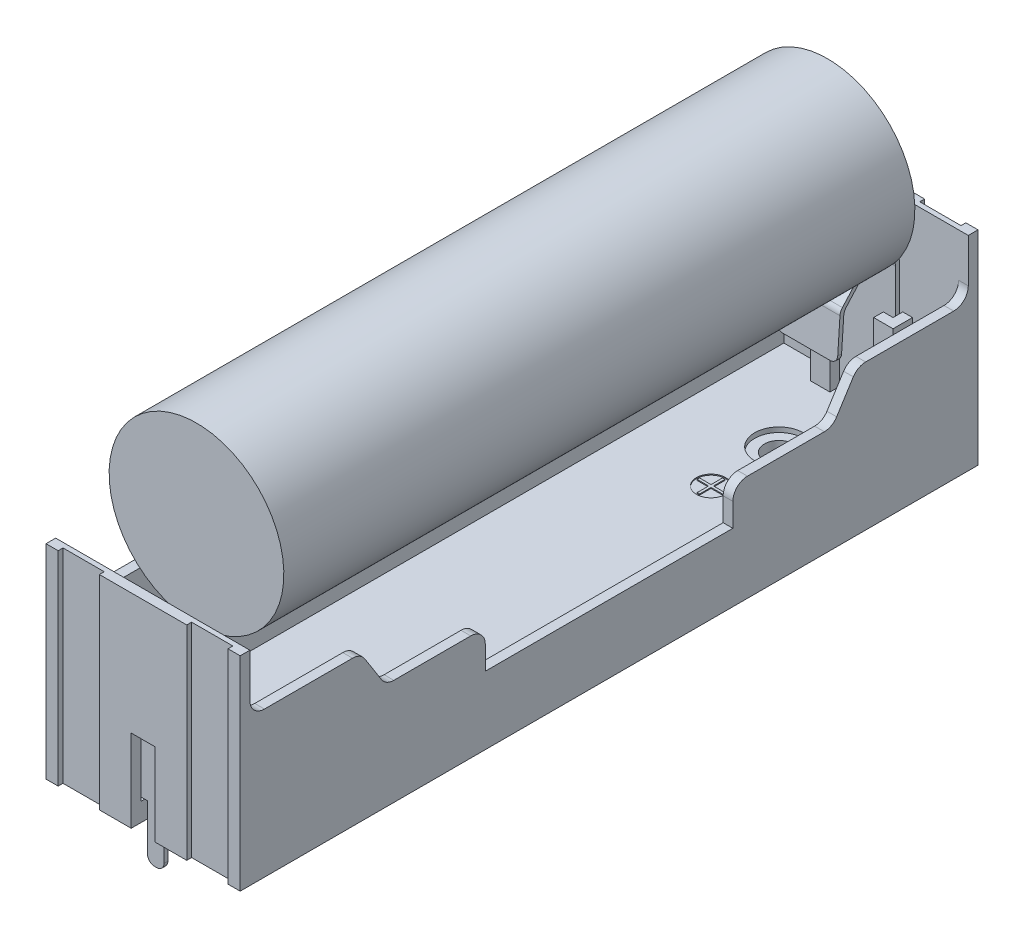
SolidWorks part; units mm, degrees
material "ABS"
ref_plane "Спереди" through (0, 0, 0) normal (0, 0, 1) x (1, 0, 0)
ref_plane "Сверху" through (0, 0, 0) normal (0, 1, 0) x (1, 0, 0)
ref_plane "Справа" through (0, 0, 0) normal (1, 0, 0) x (0, 0, -1)
other "Configuration Table"
sketch "Эскиз1" plane through (0, 0, 0) normal (0, 1, 0) x (1, 0, 0)
  line L1 (-10, 38) -> (10, 38)
  line L2 (-10, 38) -> (-10, -38)
  line L3 (-10, -38) -> (10, -38)
  line L4 (10, 38) -> (10, -38)
  line L5 (-10, 38) -> (10, -38) construction
  line L6 (-10, -38) -> (10, 38) construction
  point P0 (0, 0)
  dimension "D1" = 76
  dimension "D2" = 20
extrude "Основа" add sketch "Эскиз1" along normal blind 21
sketch "Эскиз2" plane through (0, 0, 0) normal (0, 1, 0) x (1, 0, 0)
  line L1 (10, 38) -> (-10, 38) construction
  line L2 (-4.5, 38) -> (-4.5, 37.5)
  line L3 (-4.5, 37.5) -> (-8.75, 37.5)
  line L4 (-8.75, 37.5) -> (-8.75, 38)
  line L5 (-8.75, 38) -> (-10.75, 38)
  line L6 (-10.75, 38) -> (-10.75, 37.5)
  line L13 (-10.75, 38) -> (-10, 38)
  line L14 (-10, 38) -> (-10, 46.5071)
  line L15 (-10, 46.5071) -> (10, 46.5071)
  line L16 (0, 46.5071) -> (0, 38)
  line L17 (4.5, 38) -> (-4.5, 38)
  line L18 (10, 38) -> (10, 46.5071)
  line L26 (10.75, 38) -> (10.75, 37.5)
  line L27 (8.75, 38) -> (10.75, 38)
  line L28 (4.5, 38) -> (4.5, 37.5)
  line L29 (4.5, 37.5) -> (8.75, 37.5)
  line L30 (8.75, 37.5) -> (8.75, 38)
  line L31 (10.75, 38) -> (10, 38)
  line L32 (-10.75, 37.5) -> (-8.75, 37.5)
  line L33 (10.75, 37.5) -> (8.75, 37.5)
  point P22 (0, 38)
  dimension "D1" = 9
  dimension "D2" = 2
  dimension "D3" = 4.25
  dimension "D4" = 0.5
extrude "Рёбра" cut sketch "Эскиз2" along normal through all contours L29 L30 L27 L26 L18 L15 L16 L17 L28 | L17 L16 L15 L14 L13 L6 L5 L4 L3 L2 region at (-5.0396, 0, -42.1438) region at (5.0396, 0, -42.1438)
mirror "Зеркальное отражение1" about plane through (0, 0, 0) normal (0, 0, 1) of "Рёбра"
sketch "Эскиз3" plane through (0, 21, 0) normal (0, 1, 0) x (1, 0, 0)
  line L0 (9, 0) -> (-9, 0) construction
  line L1 (9, 37) -> (-9, 37)
  line L2 (9, 37) -> (9, -37)
  line L3 (9, -37) -> (-9, -37)
  line L4 (-9, 37) -> (-9, -37)
  line L5 (9, 37) -> (-9, -37) construction
  line L6 (9, -37) -> (-9, 37) construction
  point P0 (0, 0)
  point P9 (0, 0)
  dimension "D1" = 18
  dimension "D2" = 74
extrude "Отсеки" cut sketch "Эскиз3" against normal blind 19.1
sketch "Эскиз4" plane through (0, 0, 0) normal (1, 0, 0) x (0, 0, -1)
  line L0 (37, 21) -> (-37, 21) construction
  line L1 (37, 27) -> (-37, 27)
  line L2 (37, 27) -> (37, 15)
  line L3 (37, 15) -> (-37, 15)
  line L4 (-37, 27) -> (-37, 15)
  line L5 (37, 27) -> (-37, 15) construction
  line L6 (37, 15) -> (-37, 27) construction
  line L7 (-37, 1.9) -> (-37, 21) construction
  point P0 (0, 21)
  dimension "D1" = 15
extrude "Уменьшение внутренних стенок" cut sketch "Эскиз4" against normal blind 15 and the other way blind 15
sketch "Эскиз5" plane through (10, 0, 0) normal (1, 0, 0) x (0, 0, -1)
  line L0 (-38, 21) -> (-35.6, 21)
  line L1 (-38, 21) -> (-37, 21) construction
  line L2 (-35.6, 21) -> (-35.6, 15)
  line L3 (-35.6, 15) -> (-25.6, 15)
  line L4 (-25.6, 15) -> (-23, 10.9)
  line L5 (-23, 10.9) -> (-12.75, 10.9)
  line L6 (-12.75, 10.9) -> (-12.75, 7)
  line L7 (-12.75, 7) -> (12.75, 7)
  line L8 (0, 7) -> (0, 0) construction
  line L9 (-35.6, 21) -> (35.6, 21)
  line L10 (12.75, 10.9) -> (12.75, 7)
  line L11 (23, 10.9) -> (12.75, 10.9)
  line L12 (25.6, 15) -> (23, 10.9)
  line L13 (35.6, 15) -> (25.6, 15)
  line L14 (35.6, 21) -> (35.6, 15)
  line L15 (-38, 21) -> (-37, 21) construction
  point P20 (0, 21)
  line M12 (38, 21) -> (37, 21)
  dimension "D1" = 12.75
  dimension "D2" = 10.25
  dimension "D3" = 2.4
  dimension "D4" = 10
  dimension "D5" = 6
  dimension "D6" = 3.9
  dimension "D7" = 7
extrude "Уменьшение внешних стенок" cut sketch "Эскиз5" against normal blind 15 contours L14 L2 L3 L4 L5 L6 L7 L10 L11 L12 L13 M12 region at (10, 15.384, 0)
fillet "Скругление2" radius 1.5 8 edges at (9.5, 10.9, -23) (9.5, 10.9, -12.75) (9.5, 10.9, 12.75) (9.5, 10.9, 23) (9.5, 15, -37) (9.5, 15, -25.6) (9.5, 15, 37) (9.5, 15, 25.6)
mirror "Зеркальное отражение2" about plane through (0, 0, 0) normal (1, 0, 0) of "Скругление2", "Уменьшение внешних стенок"
sketch "Эскиз6" plane through (0, 0, 0) normal (0, 1, 0) x (1, 0, 0)
  line L0 (-4.5, -38) -> (4.5, -38) construction
  line L1 (-1.225, -41.5) -> (1.225, -41.5)
  line L2 (-1.225, -41.5) -> (-1.225, -34.5)
  line L3 (-1.225, -34.5) -> (1.225, -34.5)
  line L4 (1.225, -41.5) -> (1.225, -34.5)
  line L5 (-1.225, -41.5) -> (1.225, -34.5) construction
  line L6 (-1.225, -34.5) -> (1.225, -41.5) construction
  line L7 (-10, 0) -> (10, 0) construction
  line L8 (10, -38) -> (10, 38) construction
  line L27 (-1.225, 34.5) -> (1.225, 41.5) construction
  line L28 (-1.225, 41.5) -> (1.225, 34.5) construction
  line L37 (1.225, 41.5) -> (1.225, 34.5)
  line L38 (-1.225, 34.5) -> (1.225, 34.5)
  line L39 (-1.225, 41.5) -> (-1.225, 34.5)
  line L40 (-1.225, 41.5) -> (1.225, 41.5)
  point P0 (0, -38)
  point P13 (0, 0)
  point P42 (0, 38)
  dimension "D1" = 2.45
  dimension "D2" = 3.5
extrude "Вырезы под контакты" cut sketch "Эскиз6" along normal blind 8.5
sketch "Эскиз11" plane through (0, 0, 0) normal (0, 1, 0) x (1, 0, 0)
  line L0 (0, 27.5) -> (0, -27.5) construction
  line L1 (1.5, -27.5) -> (-1.5, -27.5) construction
  line L3 (1.5, 27.5) -> (-1.5, 27.5) construction
  circle A1 centre (0, 27.5) radius 1.5
  circle A4 centre (0, -27.5) radius 1.5
  point P0 (0, 0)
  point P13 (0, 0)
  dimension "D2" = 3
  dimension "D1" = 55
extrude "Крепежные отверстия" cut sketch "Эскиз11" along normal through all
sketch "Эскиз12" plane through (0, 0, 0) normal (0, 1, 0) x (1, 0, 0)
  circle A1 centre (0, 27.5) radius 1.5 construction
  circle A4 centre (0, -27.5) radius 1.5 construction
  circle A7 centre (0, 27.5) radius 1.5
  circle A10 centre (0, -27.5) radius 1.5
  circle A13 centre (0, 27.5) radius 2.8
  circle A16 centre (0, -27.5) radius 2.8
  dimension "D1" = 1.3
extrude "Юбки отверстий" add sketch "Эскиз12" against normal blind 0.3
sketch "Эскиз13" plane through (0, 1.9, 0) normal (0, 1, 0) x (1, 0, 0)
  circle A1 centre (0, -27.5) radius 1.5 construction
  circle A3 centre (0, 27.5) radius 1.5 construction
  circle A6 centre (0, -27.5) radius 1.5
  circle A8 centre (0, 27.5) radius 1.5
  circle A13 centre (0, -27.5) radius 2.5
  circle A15 centre (0, 27.5) radius 2.5
  dimension "D1" = 1
extrude "Вырез-Вытянуть17" cut sketch "Эскиз13" against normal blind 0.5
sketch "Эскиз14" plane through (0, 1.9, 0) normal (0, 1, 0) x (1, 0, 0)
  line L0 (0, 20.5) -> (0, -20.5) construction
  line L3 (1.5, 20.5) -> (0, 20.5) construction
  line L4 (0, -20.5) -> (0, -19) construction
  line L5 (0, 19) -> (0, 20.5) construction
  line L8 (0.125, -19.2) -> (-0.125, -19.2)
  line L9 (0.125, -19.2) -> (0.125, -21.8)
  line L10 (0.125, -21.8) -> (-0.125, -21.8)
  line L11 (-0.125, -19.2) -> (-0.125, -21.8)
  line L12 (0.125, -19.2) -> (-0.125, -21.8) construction
  line L13 (0.125, -21.8) -> (-0.125, -19.2) construction
  line L14 (0.125, 21.8) -> (-0.125, 21.8)
  line L15 (0.125, 21.8) -> (0.125, 19.2)
  line L16 (0.125, 19.2) -> (-0.125, 19.2)
  line L17 (-0.125, 21.8) -> (-0.125, 19.2)
  line L18 (0.125, 21.8) -> (-0.125, 19.2) construction
  line L19 (0.125, 19.2) -> (-0.125, 21.8) construction
  line L20 (1.3, 20.625) -> (-1.3, 20.625)
  line L21 (1.3, 20.625) -> (1.3, 20.375)
  line L22 (1.3, 20.375) -> (-1.3, 20.375)
  line L23 (-1.3, 20.625) -> (-1.3, 20.375)
  line L24 (1.3, 20.625) -> (-1.3, 20.375) construction
  line L25 (1.3, 20.375) -> (-1.3, 20.625) construction
  circle A0 centre (0, 20.5) radius 1.5
  circle A1 centre (0, -20.5) radius 1.5
  point P0 (0, 0)
  point P2 (0, 0)
  dimension "D2" = 3
  dimension "D3" = 2.6
  dimension "D4" = 0.25
  dimension "D5" = 41
extrude "Полярность" cut sketch "Эскиз14" against normal blind 0.1 contours A1 L11 L8 L9 L10 | A0 L23 L20 L17 L14 L15 L21 L22 L16 region at (-1.4576, 1.9, -20.5) region at (-1.4576, 1.9, 20.5)
sketch "Эскиз15" plane through (0, 1.9, 0) normal (0, 1, 0) x (1, 0, 0)
  line L0 (-1.225, 37) -> (-9, 37) construction
  line L1 (-1.225, 37) -> (-1.225, 34.5) construction
  line L16 (-2.25, 35) -> (-4.25, 35)
  line L17 (-4.25, 35) -> (-4.25, 37)
  line L18 (-4.25, 37) -> (-3.25, 37)
  line L19 (-3.25, 37) -> (-3.25, 36)
  line L20 (-3.25, 36) -> (-2.25, 36)
  line L21 (-2.25, 36) -> (-2.25, 35)
  line L22 (2.25, 35) -> (2.25, 36)
  line L23 (2.25, 36) -> (3.25, 36)
  line L24 (3.25, 36) -> (3.25, 37)
  line L25 (3.25, 37) -> (4.25, 37)
  line L26 (4.25, 37) -> (4.25, 35)
  line L27 (4.25, 35) -> (2.25, 35)
  line L28 (0, 35.5) -> (0, 35) construction
  line L29 (-2.25, 35) -> (2.25, 35) construction
  line L44 (10, 0) -> (-10, 0) construction
  line L45 (-10, -12.75) -> (-10, 12.75) construction
  line L48 (-2.25, -35) -> (2.25, -35) construction
  line L49 (0, -35.5) -> (0, -35) construction
  line L64 (4.25, -35) -> (2.25, -35)
  line L65 (4.25, -37) -> (4.25, -35)
  line L66 (3.25, -37) -> (4.25, -37)
  line L67 (3.25, -36) -> (3.25, -37)
  line L68 (2.25, -36) -> (3.25, -36)
  line L69 (2.25, -35) -> (2.25, -36)
  line L70 (-2.25, -36) -> (-2.25, -35)
  line L71 (-3.25, -36) -> (-2.25, -36)
  line L72 (-3.25, -37) -> (-3.25, -36)
  line L73 (-4.25, -37) -> (-3.25, -37)
  line L74 (-4.25, -35) -> (-4.25, -37)
  line L75 (-2.25, -35) -> (-4.25, -35)
  point P4 (19.5, 35)
  point P24 (0, 35)
  point P55 (0, 0)
  point P99 (0, -35)
  dimension "D1" = 2
  dimension "D2" = 1.025
  dimension "D4" = 8.5
extrude "Пазы для контактов" add sketch "Эскиз15" along normal blind 8.9
ref_plane "Для эскиза контактов" through (0, 0, 0) normal (-1, 0, 0) x (0, 0, 1)
sketch "Эскиз16" plane through (0, 0, 0) normal (-1, 0, 0) x (0, 0, 1)
  line L1 (-38, 21) -> (-38, 0) construction
  line L3 (-36.5, 17.26) -> (-36.5, 15.9523) construction
  line L4 (-36.5, 15.9523) -> (-33.8, 17.26)
  line L5 (-33.8, 17.26) -> (-30.8, 13.9059)
  line L6 (-30.8, 13.9059) -> (-30.5, 9.4159)
  line L7 (-36.5, 17.26) -> (-33.8, 17.26) construction
  line L8 (-36.5, 15.9523) -> (-36.5, 2)
  line L10 (-36.5, 2) -> (-36.5, -3.54) construction
  line L12 (-38, 0) -> (38, 0) construction
  dimension "D1" = 20.8
  dimension "D2" = 3
  dimension "D3" = 4.5
  dimension "D4" = 6
  dimension "D5" = 5.7
  dimension "D6" = 2.7
  dimension "D7" = 2
  dimension "D8" = 1.5
  dimension "D9" = 13.9523
extrude "Контакт" add sketch "Эскиз16" along normal mid plane 6.4 thin thin type mid plane wall 0.4
sketch "Эскиз17" plane through (0, 2, 0) normal (0, -1, 0) x (1, 0, 0)
  line L0 (0, -36.7) -> (0, -36.3) construction
  line L1 (-3.2, -36.7) -> (3.2, -36.7) construction
  line L2 (-3.2, -36.3) -> (3.2, -36.3) construction
  line L4 (0.85, -36.3) -> (-0.85, -36.3)
  line L5 (0.85, -36.3) -> (0.85, -36.7)
  line L6 (0.85, -36.7) -> (-0.85, -36.7)
  line L7 (-0.85, -36.3) -> (-0.85, -36.7)
  line L8 (0.85, -36.3) -> (-0.85, -36.7) construction
  line L9 (0.85, -36.7) -> (-0.85, -36.3) construction
  point P6 (0, -36.5)
  dimension "D1" = 1.7
extrude "Штырёк для пайки" add sketch "Эскиз17" along normal blind 5.5
fillet "Скругление3" radius 1 6 edges at (0, 13.8239, -30.995) (0, 13.9879, -30.605) (0, 17.0143, -33.8485) (0, 17.5057, -33.7515) (0, 15.827, -36.3) (0, 16.0777, -36.7)
fillet "Скругление4" radius 0.75 6 edges at (3.2, 2, -36.5) (0.85, -3.5, -36.5) (-0.85, -3.5, -36.5) (-3.2, 2, -36.5) (3.2, 9.4159, -30.5) (-3.2, 9.4159, -30.5)
mirror "Mirror1" about plane through (0, 0, 0) normal (0, 0, 1) of bodies 125
sketch "Эскиз18" plane through (0, 0, 0) normal (0, 0, 1) x (1, 0, 0)
  circle A0 centre (0, 25.02) radius 9
  dimension "D1" = 18
  dimension "D2" = 25.02
extrude "Бобышка-Вытянуть1" add sketch "Эскиз18" along normal mid plane 65
equation "\"D1@Эскиз5\"=25.5/2"
